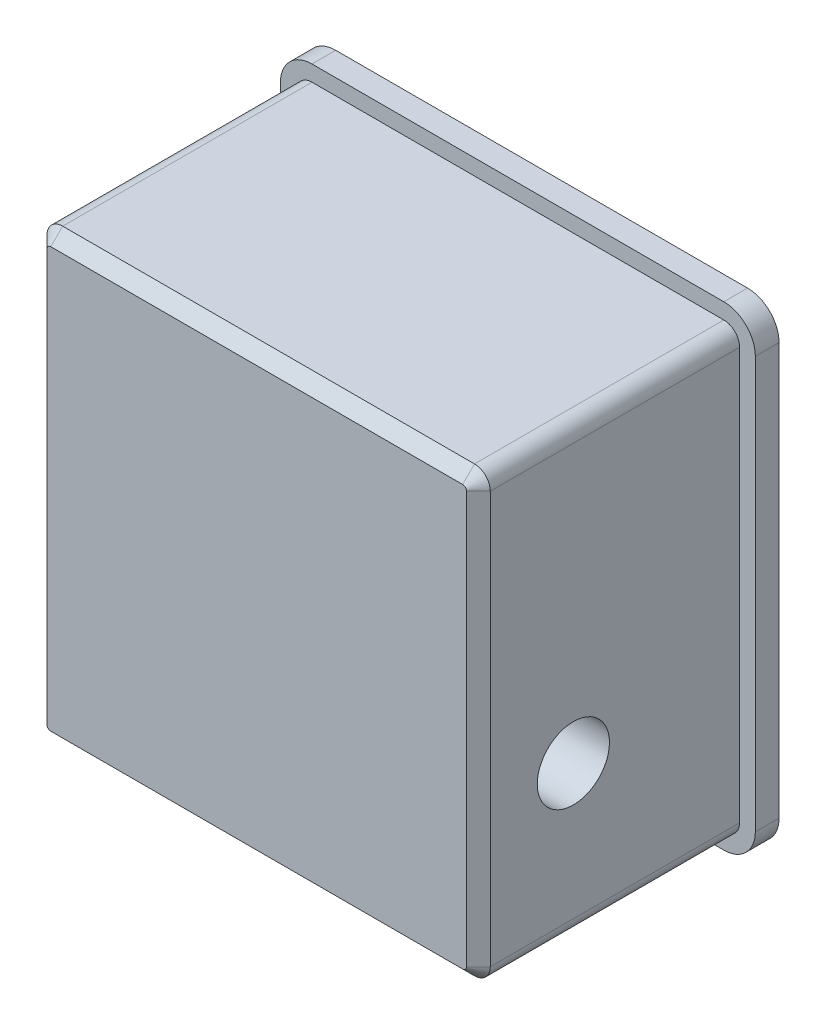
SolidWorks part; units mm, degrees
material "ABS"
ref_plane "Front Plane" through (0, 0, 0) normal (0, 0, 1) x (1, 0, 0)
ref_plane "Top Plane" through (0, 0, 0) normal (0, 1, 0) x (1, 0, 0)
ref_plane "Right Plane" through (0, 0, 0) normal (1, 0, 0) x (0, 0, -1)
sketch "Sketch1" plane through (0, 0, 0) normal (0, 0, 1) x (1, 0, 0)
  line L0 (27.5336, 29.6418) -> (-27.5336, 29.6418)
  line L1 (27.5336, 31.75) -> (-27.5336, 31.75)
  line L2 (31.75, 27.5336) -> (31.75, -27.5336)
  line L3 (27.5336, -31.75) -> (-27.5336, -31.75)
  line L4 (-31.75, 27.5336) -> (-31.75, -27.5336)
  line L5 (31.75, 31.75) -> (-31.75, -31.75) construction
  line L6 (31.75, -31.75) -> (-31.75, 31.75) construction
  line L7 (-29.6418, 27.5336) -> (-29.6418, -27.5336)
  line L12 (27.5336, -29.6418) -> (-27.5336, -29.6418)
  line L13 (29.6418, 27.5336) -> (29.6418, -27.5336)
  arc A0 (-27.5336, -31.75) -> (-31.75, -27.5336) centre (-27.5336, -27.5336) cw
  arc A1 (31.75, -27.5336) -> (27.5336, -31.75) centre (27.5336, -27.5336) cw
  arc A2 (27.5336, 31.75) -> (31.75, 27.5336) centre (27.5336, 27.5336) cw
  arc A3 (-27.5336, 31.75) -> (-31.75, 27.5336) centre (-27.5336, 27.5336) ccw
  arc A4 (-27.5336, 29.6418) -> (-29.6418, 27.5336) centre (-27.5336, 27.5336) ccw
  arc A5 (-27.5336, -29.6418) -> (-29.6418, -27.5336) centre (-27.5336, -27.5336) cw
  arc A6 (29.6418, -27.5336) -> (27.5336, -29.6418) centre (27.5336, -27.5336) cw
  arc A7 (27.5336, 29.6418) -> (29.6418, 27.5336) centre (27.5336, 27.5336) cw
  point P0 (0, 0)
  dimension "D1" = 63.5
  dimension "D4" = 2.1082
  dimension "D3" = 4.2164
  dimension "D2" = 63.5
extrude "Boss-Extrude1" add sketch "Sketch1" along normal blind 38.1 contours A7 L0 A4 L7 A5 L12 A6 L13 region at (0, 0, 0)
extrude "Boss-Extrude2" add sketch "Sketch1<3>" along normal blind 3.175
sketch "Sketch1<3>" plane through (0, 0, 0) normal (0, 0, 1) x (1, 0, 0) same geometry as "Sketch1"
sketch "Sketch2" plane through (29.6418, 0, 0) normal (1, 0, 0) x (0, 0, -1)
  line L0 (-3.175, -31.75) -> (0, -31.75) construction
  line L1 (-3.175, -27.5336) -> (-3.175, 27.5336) construction
  circle A0 centre (-25.4, -9.525) radius 4.826
  dimension "D2" = 9.652
  dimension "D1" = 22.225
  dimension "D3" = 22.225
extrude "Cut-Extrude1" cut sketch "Sketch2" against normal through all
chamfer "Chamfer1" distance 1.5875 angle 45 8 edges at (0, 29.6418, 38.1) (29.0243, 29.0243, 38.1) (-29.0243, 29.0243, 38.1) (29.6418, 0, 38.1) (-29.6418, 0, 38.1) (29.0243, -29.0243, 38.1) (-29.0243, -29.0243, 38.1) (0, -29.6418, 38.1)
